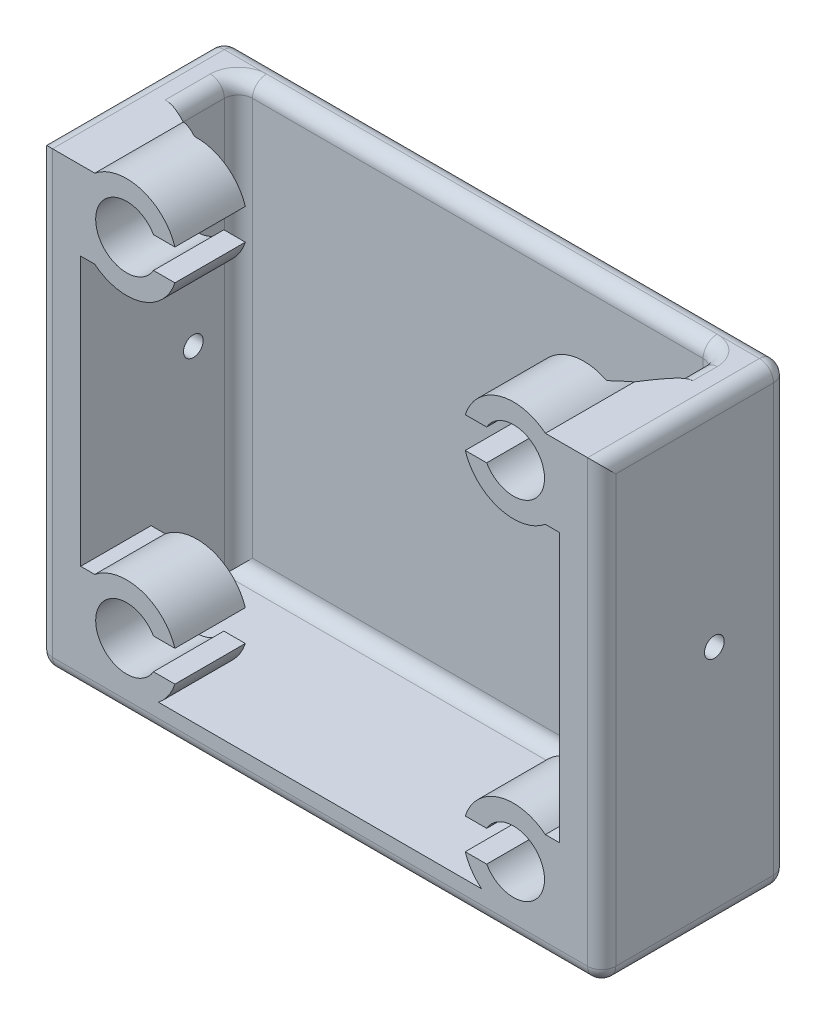
SolidWorks part; units mm, degrees
ref_plane "Plano frontal" through (0, 0, 0) normal (0, 0, 1) x (1, 0, 0)
ref_plane "Plano superior" through (0, 0, 0) normal (0, 1, 0) x (1, 0, 0)
ref_plane "Plano direito" through (0, 0, 0) normal (1, 0, 0) x (0, 0, -1)
sketch "Esboço1" plane through (0, 0, 0) normal (0, 0, 1) x (1, 0, 0)
  line L0 (0, 0) -> (-9, 0) construction
  line L2 (0, 2.75) -> (-4.7631, 2.75) construction
  line L3 (-4.7631, 2.75) -> (-8.5696, 2.75)
  line L4 (0, -2.75) -> (-4.7631, -2.75) construction
  line L5 (-4.7631, -2.75) -> (-8.5696, -2.75)
  line L6 (0, -2.75) -> (4.7631, -2.75) construction
  line L7 (4.7631, -2.75) -> (8.5696, -2.75) construction
  line L8 (0, 2.75) -> (4.7631, 2.75) construction
  line L9 (4.7631, 2.75) -> (8.5696, 2.75) construction
  line L10 (15.6569, -7) -> (15.6569, 7) construction
  line L11 (15.6569, 7) -> (5.6569, 7)
  line L12 (15.6569, -7) -> (5.6569, -7)
  line L13 (15.6569, 7) -> (15.6569, -7)
  line L14 (0, 0) -> (0, -61.7) construction
  line L15 (0, -30.85) -> (18.4015, -30.85) construction
  line L16 (15.6569, -54.7) -> (15.6569, -68.7) construction
  line L17 (4.7631, -64.45) -> (8.5696, -64.45) construction
  line L18 (0, -64.45) -> (4.7631, -64.45) construction
  line L19 (4.7631, -58.95) -> (8.5696, -58.95) construction
  line L20 (0, -58.95) -> (4.7631, -58.95) construction
  line L21 (0, -58.95) -> (-4.7631, -58.95) construction
  line L22 (0, -64.45) -> (-4.7631, -64.45) construction
  line L23 (0, -61.7) -> (-9, -61.7) construction
  line L24 (15.6569, -68.7) -> (15.6569, -54.7)
  line L25 (15.6569, -54.7) -> (5.6569, -54.7)
  line L26 (15.6569, -68.7) -> (5.6569, -68.7)
  line L27 (-4.7631, -58.95) -> (-8.5696, -58.95)
  line L28 (-4.7631, -64.45) -> (-8.5696, -64.45)
  arc A0 (-4.7631, -2.75) -> (-4.7631, 2.75) centre (0, 0) ccw
  arc A1 (-8.5696, -2.75) -> (5.6569, -7) centre (0, 0) ccw
  arc A2 (5.6569, -68.7) -> (-8.5696, -64.45) centre (0, -61.7) cw
  arc A3 (5.6569, 7) -> (-8.5696, 2.75) centre (0, 0) ccw
  arc A4 (-8.5696, -58.95) -> (5.6569, -54.7) centre (0, -61.7) cw
  arc A5 (-4.7631, -58.95) -> (-4.7631, -64.45) centre (0, -61.7) cw
  point P8 (0, 0)
  point P17 (15.6569, 0)
  point P37 (15.6569, -61.7)
  point P38 (0, -61.7)
  dimension "D1" = 11
  dimension "D2" = 18
  dimension "D3" = 5.5
  dimension "D4" = 14
  dimension "D5" = 10
  dimension "D6" = 61.7
  dimension "D7" = 5.5
  dimension "D8" = 3.8064
extrude "Ressalto-extrusão2" add sketch "Esboço1" along normal blind 12.5
ref_plane "Plano1" through (-34.3431, 0, 0) normal (1, 0, 0) x (0, 0, -1)
sketch "Esboço2" plane through (0, 0, 12.5) normal (0, 0, -1) x (-1, 0, 0)
  line L1 (-15.6569, 7) -> (-8.1569, 7)
  line L2 (-15.6569, 7) -> (-15.6569, -68.7)
  line L3 (-15.6569, -68.7) -> (-8.1569, -68.7)
  line L4 (-8.1569, 7) -> (-8.1569, -68.7)
  dimension "D1" = 7.5
extrude "Ressalto-extrusão3" add sketch "Esboço2" along normal blind 28
sketch "Esboço3" plane through (0, 0, -15.5) normal (0, 0, -1) x (-1, 0, 0)
  line L0 (34.3431, 6.875) -> (34.3431, -6.875) construction
  line L1 (-15.6569, 7) -> (34.3431, 7)
  line L2 (-15.6569, 7) -> (-15.6569, -68.7)
  line L3 (-15.6569, -68.7) -> (34.3431, -68.7)
  line L4 (34.3431, 7) -> (34.3431, -68.7)
extrude "Ressalto-extrusão4" add sketch "Esboço3" along normal blind 5
sketch "Esboço5" plane through (8.1569, 0, 0) normal (-1, 0, 0) x (0, 0, 1)
  line L0 (-15.5, -68.7) -> (-15.5, 7) construction
  circle A0 centre (-7.5, -30.85) radius 1.75
  point P4 (-15.5, -30.85)
  dimension "D1" = 3.5
  dimension "D2" = 8
extrude "Corte-extrusão2" cut sketch "Esboço5" against normal through all both and the other way through all
sketch "Esboço6" plane through (0, -68.7, 0) normal (0, -1, 0) x (1, 0, 0)
  line L0 (-34.3431, -6.875) -> (-34.3431, 6.875) construction
  line L1 (15.6569, -20.5) -> (-34.3431, -20.5)
  line L2 (15.6569, -20.5) -> (15.6569, 12.5)
  line L3 (15.6569, 12.5) -> (-34.3431, 12.5)
  line L4 (-34.3431, -20.5) -> (-34.3431, 12.5)
extrude "Ressalto-extrusão5" add sketch "Esboço6" along normal blind 5
mirror "Espelhar10" about plane through (-34.3431, 0, 0) normal (1, 0, 0) of bodies 117
fillet "Filete1" radius 2.5 17 edges at (-76.8431, 7, -7.75) (8.1569, 7, -7.75) (-34.3431, 7, -15.5) (-34.3431, -68.7, -15.5) (8.1569, -30.85, -15.5) (-76.8431, -30.85, -15.5) (-84.3431, -33.35, -20.5) (-84.3431, 7, -4) (-84.3431, -33.35, 12.5) (-84.3431, -73.7, -4) (-34.3431, -73.7, 12.5) (-34.3431, -73.7, -20.5) (15.6569, -73.7, -4) (15.6569, -33.35, 12.5) (-34.3431, 7, -20.5) (15.6569, 7, -4) (15.6569, -33.35, -20.5)
chamfer "Chanfro1" distance 5 angle 60 4 edges at (8.8891, 6.2678, 0) (8.1569, -1.25, 0) (-77.5754, 6.2678, 0) (-76.8431, -1.25, 0) first distance on face at (2.125, 0.5575, 0) first distance on face at (-77.8343, 6.0089, -6.5) first distance on face at (-76.8431, -29.1, -7.5)
ref_plane "Plano3" [suppressed] through (0, 0, 32.55) normal (0, 0, 1) x (1, 0, 0)
mirror "Espelhar9" [suppressed] about plane through (0, 0, 32.55) normal (0, 0, 1) of bodies 118 112
delete or keep bodies "Corpo-Excluir/Manter 2" [suppressed] type delete bodies bodies 118
